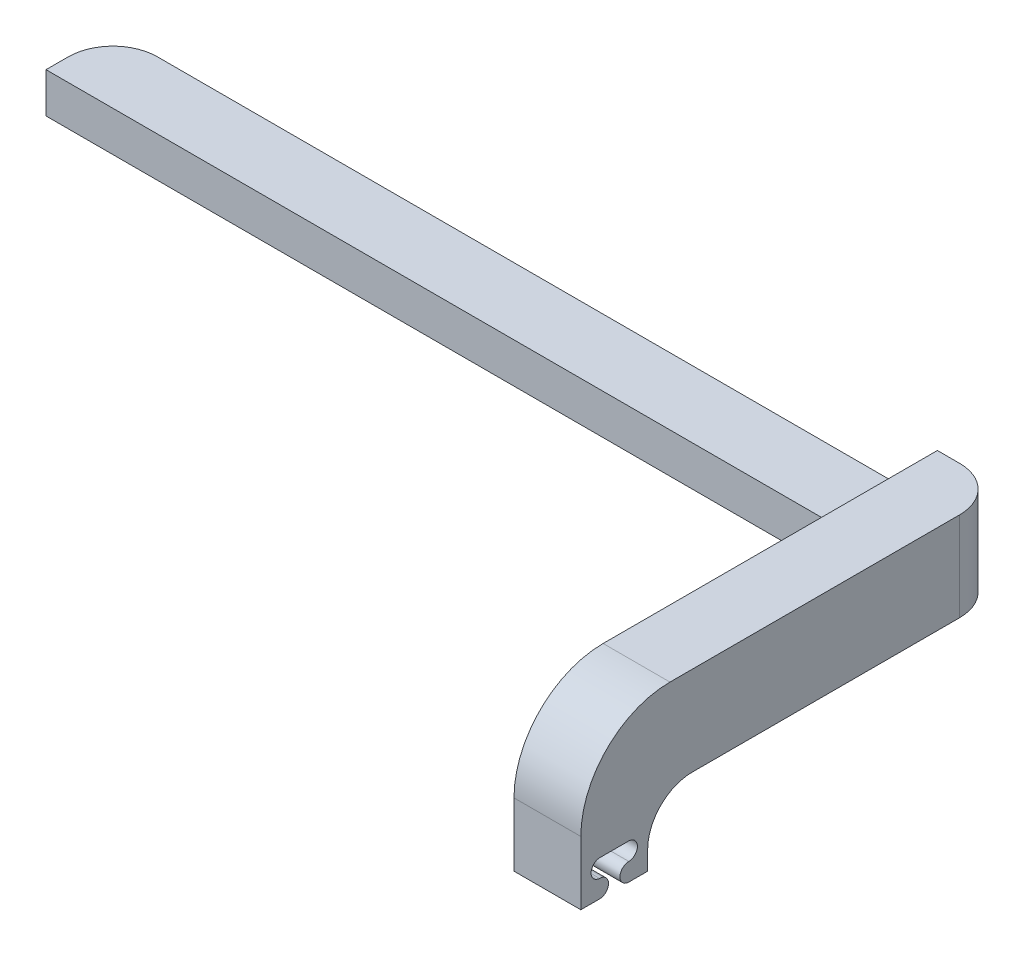
SolidWorks part; units mm, degrees
ref_plane "Front Plane" through (0, 0, 0) normal (0, 0, 1) x (1, 0, 0)
ref_plane "Top Plane" through (0, 0, 0) normal (0, 1, 0) x (1, 0, 0)
ref_plane "Right Plane" through (0, 0, 0) normal (1, 0, 0) x (0, 0, -1)
sketch "Sketch1" plane through (0, 0, 0) normal (0, 0, 1) x (1, 0, 0)
  line L6 (48.0544, -51.8775) -> (48.2794, -51.8775)
  line L19 (51.6669, -45.8775) -> (59.1669, -45.8775)
  line L20 (51.6669, -45.8775) -> (44.6669, -45.8775) construction
  line L21 (41.9169, -64.1275) -> (54.4169, -64.1275)
  line L22 (41.9169, -64.1275) -> (41.9169, -69.3775)
  line L24 (54.4169, -64.1275) -> (54.4169, -69.3775)
  line L25 (59.1669, -69.3775) -> (37.1669, -69.3775)
  line L28 (37.1669, -45.8775) -> (44.6669, -45.8775)
  line L32 (44.6669, -45.8775) -> (51.6669, -45.8775)
  line L33 (37.1669, -45.8775) -> (37.1669, -69.3775)
  line L34 (59.1669, -45.8775) -> (59.1669, -69.3775)
  line L35 (59.1669, -50.8775) -> (37.1669, -50.8775) construction
  line L36 (48.1669, -50.8775) -> (48.1669, 64.3396) construction
  line L38 (48.0544, -49.8775) -> (48.2794, -49.8775)
  arc A0 (48.2794, -51.8775) -> (48.2794, -49.8775) centre (52.6669, -50.8775) ccw
  arc A1 (48.0544, -49.8775) -> (48.0544, -51.8775) centre (43.6669, -50.8775) ccw
  point P0 (0, 0)
  point P9 (51.5, -66.7525)
  point P11 (41.9169, -66.7525)
  dimension "D7" = 9
  dimension "D3" = 12.5
  dimension "D4" = 5
  dimension "D8" = 7.5
  dimension "D9" = 7.5
  dimension "D10" = 23.5
  dimension "D11" = 5.25
  dimension "D12" = 4.75
  dimension "D13" = 9
  dimension "D5" = 22
extrude "pusher base" add sketch "Sketch1" along normal blind 15 contours L32 L28 L19 A1 A0 L21 L24 L22 region at (48.1669, -58.4331, 0)
sketch "Sketch3" plane through (0, -64.1275, 0) normal (0, -1, 0) x (1, 0, 0)
  line L0 (48.1669, 15) -> (48.1669, 0) construction
  line L1 (41.9169, 15) -> (54.4169, 15) construction
  line L2 (41.9169, 0) -> (54.4169, 0) construction
  circle A0 centre (48.1669, 7.5) radius 1.95
  point P10 (48.1669, 7.5)
  dimension "D1" = 3.9
extrude "screw hole" cut sketch "Sketch3" against normal blind 7.5
ref_plane "Plane1" through (0, 0, 7.5) normal (0, 0, 1) x (1, 0, 0)
sketch "Sketch6" plane through (0, 0, 7.5) normal (0, 0, 1) x (1, 0, 0)
  line L0 (41.9169, -64.1275) -> (54.4169, -64.1275) construction
  line L5 (37.1669, -45.8775) -> (59.1669, -45.8775) construction
  line L6 (44.4169, -25.6275) -> (51.9169, -25.6275)
  line L11 (44.4169, -25.6275) -> (44.4169, -45.8775)
  line L12 (44.4169, -45.8775) -> (51.9169, -45.8775)
  line L13 (51.9169, -25.6275) -> (51.9169, -45.8775)
  line L14 (48.1669, -64.1275) -> (48.1669, -27.6275) construction
  line L15 (51.9169, -25.6275) -> (44.4169, -25.6275)
  line L16 (51.9169, -25.6275) -> (51.9169, -15.6275)
  line L17 (51.9169, -15.6275) -> (44.4169, -15.6275)
  line L18 (44.4169, -25.6275) -> (44.4169, -15.6275)
  point P2 (48.1669, -25.6275)
  point P8 (48.1669, -45.8775)
  dimension "D1" = 7.5
  dimension "D3" = 7.5
  dimension "D4" = 10
  dimension "D5" = 38.5
extrude "pusher head" add sketch "Sketch6" along normal mid plane 7.5 contours L18 L15 L6 L16 L17 | L13 L6 L12 | L11 L12 L6 region at (48.1669, -20.6275, 7.5) region at (48.1669, -35.7525, 7.5)
fillet "Fillet1" radius 2 2 edges at (48.1669, -45.8775, 0) (48.1669, -45.8775, 15)
sketch "Sketch12" plane through (44.4169, 0, 0) normal (-1, 0, 0) x (0, 0, 1)
  line L0 (7.5, -15.6275) -> (7.5, -45.8775) construction
  line L1 (11.25, -15.6275) -> (3.75, -15.6275) construction
  line L2 (11.25, -45.8775) -> (3.75, -45.8775) construction
  line L3 (3.75, -30.7525) -> (11.25, -30.7525) construction
  line L4 (3.75, -45.8775) -> (3.75, -15.6275) construction
  line L5 (11.25, -45.8775) -> (11.25, -15.6275) construction
  line L6 (5.8585, -32.7525) -> (3.75, -32.7525)
  line L7 (5.8585, -28.7525) -> (9.1415, -28.7525)
  line L8 (9.1415, -32.7525) -> (11.25, -32.7525)
  line L9 (3.75, -32.7025) -> (5.8585, -32.7025)
  line L10 (11.25, -32.7025) -> (9.1415, -32.7025)
  arc A0 (5.8585, -32.7525) -> (5.8585, -30.7525) centre (5.8585, -31.7525) ccw
  arc A1 (5.8585, -28.7525) -> (5.8585, -30.7525) centre (5.8585, -29.7525) ccw
  arc A2 (9.1415, -32.7525) -> (9.1415, -30.7525) centre (9.1415, -31.7525) cw
  arc A3 (9.1415, -28.7525) -> (9.1415, -30.7525) centre (9.1415, -29.7525) cw
  arc A4 (5.8585, -30.7525) -> (5.8585, -32.7025) centre (5.8585, -31.7275) cw
  arc A5 (9.1415, -30.7525) -> (9.1415, -32.7025) centre (9.1415, -31.7275) ccw
  arc A6 (5.8585, -30.7525) -> (5.8585, -28.7525) centre (5.9027, -29.7525) cw
  arc A7 (9.1415, -30.7525) -> (9.1415, -28.7525) centre (9.0973, -29.7525) ccw
  point P25 (7.5, -28.7525)
  line M4 (3.75, -15.6275) -> (3.75, -45.8775)
  line M5 (3.75, -45.8775) -> (11.25, -45.8775)
  line M6 (11.25, -45.8775) -> (11.25, -15.6275)
  dimension "D1" = 2
  dimension "D2" = 0.05
sketch "Sketch9" plane through (51.9169, 0, 0) normal (1, 0, 0) x (0, 0, -1)
  line L1 (-3.75, -15.6275) -> (36.25, -15.6275)
  line L2 (-3.75, -15.6275) -> (-3.75, -25.6275)
  line L3 (-3.75, -25.6275) -> (36.25, -25.6275)
  line L4 (36.25, -15.6275) -> (36.25, -25.6275)
  dimension "D1" = 10
  dimension "D2" = 40
extrude "Boss-Extrude1" add sketch "Sketch9" against normal blind 7.5
sketch "Sketch10" plane through (0, 0, -36.25) normal (0, 0, -1) x (-1, 0, 0)
  line L1 (-44.4169, -21.1275) -> (48.0831, -21.1275)
  line L2 (-44.4169, -21.1275) -> (-44.4169, -25.6275)
  line L3 (-44.4169, -25.6275) -> (48.0831, -25.6275)
  line L4 (48.0831, -21.1275) -> (48.0831, -25.6275)
  point P5 (0, 0)
  dimension "D1" = 4.5
  dimension "D2" = 92.5
extrude "Boss-Extrude2" add sketch "Sketch10" against normal blind 7.5
fillet "Fillet7" radius 10 1 edges at (48.1669, -15.6275, 11.25)
fillet "Fillet8" radius 5 3 edges at (-48.0831, -23.3775, -36.25) (51.9169, -20.6275, -36.25) (48.1669, -25.6275, 3.75)
fillet "Fillet9" radius 5 2 edges at (48.1669, -45.8775, 3.75) (48.1669, -45.8775, 11.25)
ref_plane "Plane2" through (0, 0, 25) normal (0, 0, 1) x (1, 0, 0)
extrude "Cut-Extrude1" cut sketch "Sketch12" against normal blind 10 contours A2 A7 L7 A6 A0 L6 L8 M4 M5 M6 region at (44.4169, -38.2639, 7.5)
sketch "Sketch13" plane through (0, -32.7525, 0) normal (0, -1, 0) x (1, 0, 0)
  line L1 (32.2204, 0) -> (63.4781, 0)
  line L2 (32.2204, 0) -> (32.2204, 16.4605)
  line L3 (32.2204, 16.4605) -> (63.4781, 16.4605)
  line L4 (63.4781, 0) -> (63.4781, 16.4605)
extrude "Cut-Extrude2" cut sketch "Sketch13" along normal blind 40
equation "\"PusherHeight\"=2"
equation "\"PusherWidth\"=11"
equation "\"PusherLongWidth\"=5"
equation "\"RodDiameter\"=0.5"
equation "\"HookLength\"=2.01152"
equation "\"HookHeight\"=0.999652"
equation "\"HookInnerLength\"=2"
equation "\"RodHeightDistance\"=0.4276"
equation "\"RodWidthDistance\"=0.75"
equation "\"PusherDepth\"=2"
equation "\"BuckleShaftDiameter\"=0.383646"
equation "\"BeltBuckleDistance\"=1.5"
equation "\"DowelDiameter\"=0.9"
equation "\"D7@Sketch1\"=\"DowelDiameter\""
equation "\"RodSeperationDistance\"=3.98"
equation "\"BuckleNutDiameter\"=0.39"
equation "\"D1@Sketch3\"=\"BuckleNutDiameter\""
equation "\"belt hole width\"=1.4"
equation "\"pusher height\"=3.5175"
equation "\"pusher slot width\"=0.75"
equation "\"D1@Sketch6\"=\"pusher slot width\""
equation "\"pushing bar width\"=1"
equation "\"D4@Sketch6\"=\"pushing bar width\""
equation "\"doweltotop\"=0.5"
equation "\"D4@Sketch1\"=\"doweltotop\""
equation "\"dowel separation\"=0.9"
equation "\"D13@Sketch1\"=\"dowel separation\""
